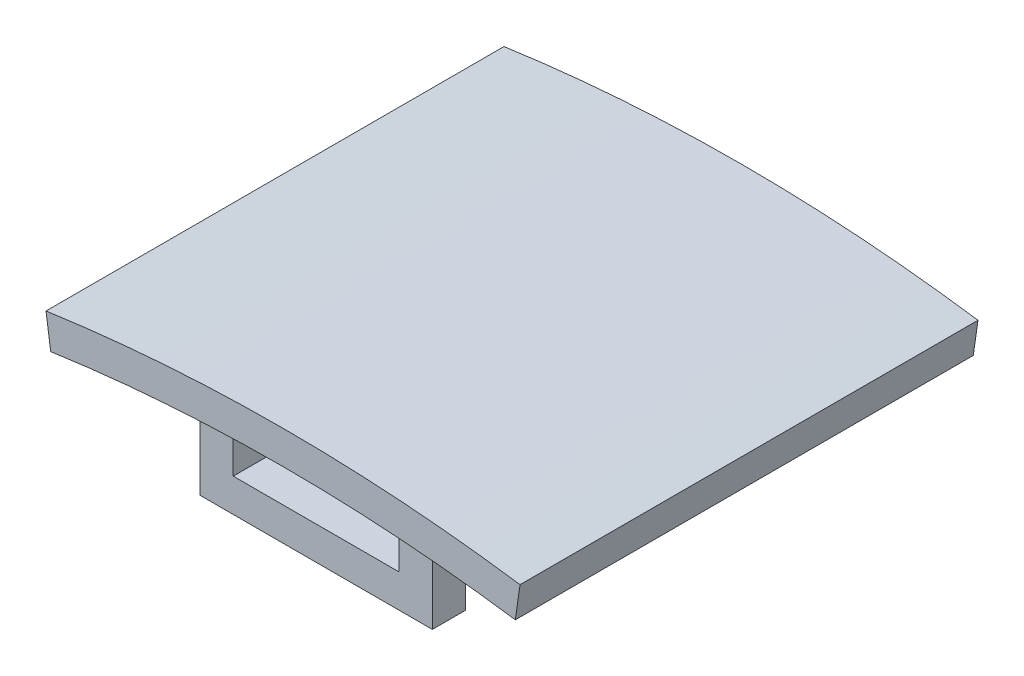
SolidWorks part; units mm, degrees
material "ABS"
ref_plane "Спереди" through (0, 0, 0) normal (0, 0, 1) x (1, 0, 0)
ref_plane "Сверху" through (0, 0, 0) normal (0, 1, 0) x (1, 0, 0)
ref_plane "Справа" through (0, 0, 0) normal (1, 0, 0) x (0, 0, -1)
sketch "Эскиз1" plane through (0, 0, 0) normal (0, 0, 1) x (1, 0, 0)
  line L0 (0, 0) -> (-14, 0) construction
  line L1 (0, 0) -> (0, -14.2099) construction
  line L2 (14, 0) -> (0, 0) construction
  line L3 (0, 0) -> (0, 1) construction
  line L4 (-14, 0) -> (-14.2843, 1.9797)
  line L5 (14, 0) -> (14.2843, 1.9797)
  arc A0 (-14, 0) -> (14, 0) centre (0, -97.5) cw
  arc A1 (-14.2843, 1.9797) -> (14.2843, 1.9797) centre (0, -97.5) cw
  dimension "D2" = 1
  dimension "D1" = 28
  dimension "D3" = 2
extrude "Бобышка-Вытянуть1" add sketch "Эскиз1" along normal blind 13.8 and the other way blind 13.8
sketch "Эскиз2" plane through (0, 0, 13.8) normal (0, 0, 1) x (1, 0, 0)
  line L0 (0, -2) -> (0, 0) construction
  line L1 (0, -3) -> (0, -5) construction
  line L3 (-7, 1) -> (7, 1)
  line L4 (-7, 1) -> (-7, -5)
  line L5 (-7, -5) -> (7, -5)
  line L6 (7, 1) -> (7, -5)
  line L7 (-7, 1) -> (7, -5) construction
  line L8 (-7, -5) -> (7, 1) construction
  line L9 (-5, -3) -> (5, -3)
  line L10 (-5, -3) -> (-5, -1)
  line L11 (-5, -1) -> (5, -1)
  line L12 (5, -3) -> (5, -1)
  line L13 (-5, -3) -> (5, -1) construction
  line L14 (-5, -1) -> (5, -3) construction
  dimension "D6" = 2
  dimension "D1" = 14
  dimension "D2" = 6
  dimension "D3" = 2
  dimension "D4" = 10
  dimension "D5" = 2
extrude "Бобышка-Вытянуть2" add sketch "Эскиз2" along direction (0, 0, 1) on the side against the normal offset from surface (2 mm away) 4 from offset 2 up to face at (0, 1.4949, 13.8) offset against normal yes
mirror "Зеркальное отражение1" about plane through (0, 0, 0) normal (0, 0, 1) of "Бобышка-Вытянуть2"
sketch "Эскиз3" plane through (0, 0, 0) normal (0, 1, 0) x (1, 0, 0)
  circle A0 centre (0, 0) radius 3
  dimension "D1" = 6
extrude "Бобышка-Вытянуть3" add sketch "Эскиз3" along normal blind 1 and the other way blind 3
sketch "Эскиз4" plane through (0, -3, 0) normal (0, -1, 0) x (-1, 0, 0)
  line L0 (0, 0) -> (-3, 0) construction
  line L1 (-1.1228, -0.9947) -> (-2.0922, -2.15)
  line L2 (-1.1228, 0.9947) -> (-2.0922, 2.15)
  line L3 (1.4228, 0.475) -> (2.9081, 0.7369)
  line L4 (-0.3, 1.4697) -> (-0.8158, 2.8869)
  line L5 (-0.3, -1.4697) -> (-0.8158, -2.8869)
  line L6 (1.4228, -0.475) -> (2.9081, -0.7369)
  arc A0 (-2.0922, 2.15) -> (-2.0922, -2.15) centre (0, 0) ccw
  arc A1 (-1.1228, 0.9947) -> (-1.1228, -0.9947) centre (0, 0) ccw
  arc A2 (-0.3, -1.4697) -> (1.4228, -0.475) centre (0, 0) ccw
  arc A3 (2.9081, 0.7369) -> (-0.8158, 2.8869) centre (0, 0) ccw
  arc A4 (1.4228, 0.475) -> (-0.3, 1.4697) centre (0, 0) ccw
  arc A5 (-0.8158, -2.8869) -> (2.9081, -0.7369) centre (0, 0) ccw
  arc A6 (-0.3, -1.4697) -> (1.4228, -0.475) centre (0, 0) ccw
  arc A7 (-1.1228, 0.9947) -> (-1.1228, -0.9947) centre (0, 0) ccw
  arc A8 (1.4228, 0.475) -> (-0.3, 1.4697) centre (0, 0) ccw
  point P19 (0, 0)
  circle M7 centre (0, 0) radius 3
  dimension "D1" = 6
  dimension "D2" = 3
  dimension "D3" = 4.3
  dimension "D4" = 50
  dimension "D5" = 100
  dimension "D6" = 3
extrude "Бобышка-Вытянуть4" add sketch "Эскиз4" along normal blind 3 contours A2 L0 A0 L1 | A2 L5 L6 M7 | A2 L3 L4 M7 | L0 A1 L2 M7 region at (2.1143, -3, 0.867) region at (2.1143, -3, -0.867) region at (-1.0571, -3, -1.831) region at (-1.0571, -3, 1.831)
